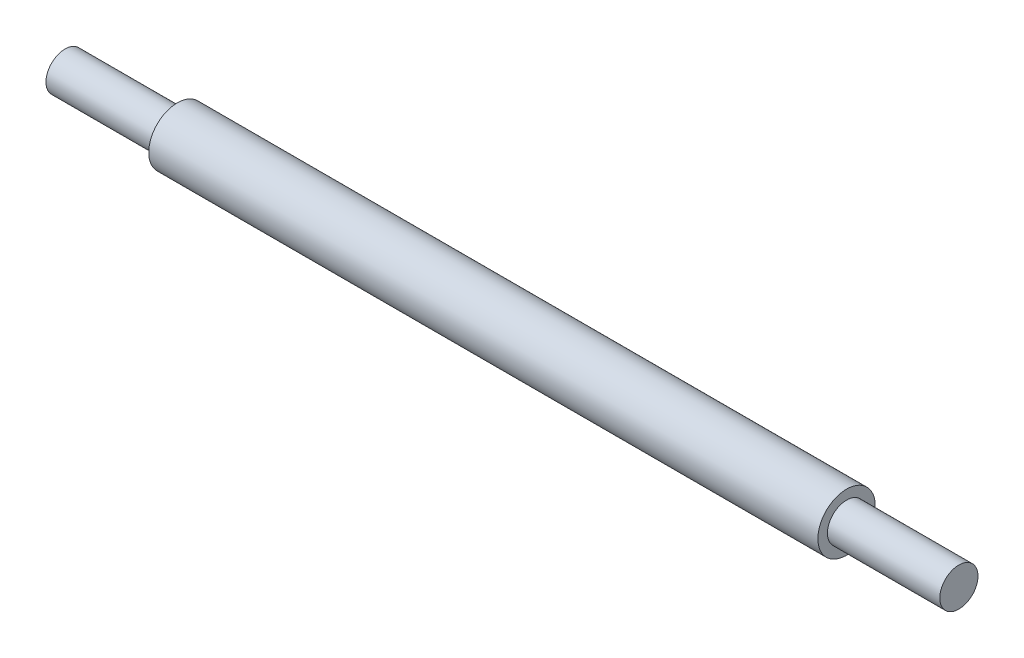
SolidWorks part; units mm, degrees
ref_plane "Front Plane" through (0, 0, 0) normal (0, 0, 1) x (1, 0, 0)
ref_plane "Top Plane" through (0, 0, 0) normal (0, 1, 0) x (1, 0, 0)
ref_plane "Right Plane" through (0, 0, 0) normal (1, 0, 0) x (0, 0, -1)
sketch "Sketch1" plane through (0, 0, 0) normal (1, 0, 0) x (0, 0, -1)
  circle A0 centre (0, 0) radius 3
extrude "Boss-Extrude1" add sketch "Sketch1" along normal blind 35 and the other way blind 35
sketch "Sketch3" plane through (0, 0, 0) normal (1, 0, 0) x (0, 0, -1)
  circle A0 centre (0, 0) radius 2
extrude "Boss-Extrude2" add sketch "Sketch3" along normal blind 46.75 and the other way blind 46.75
